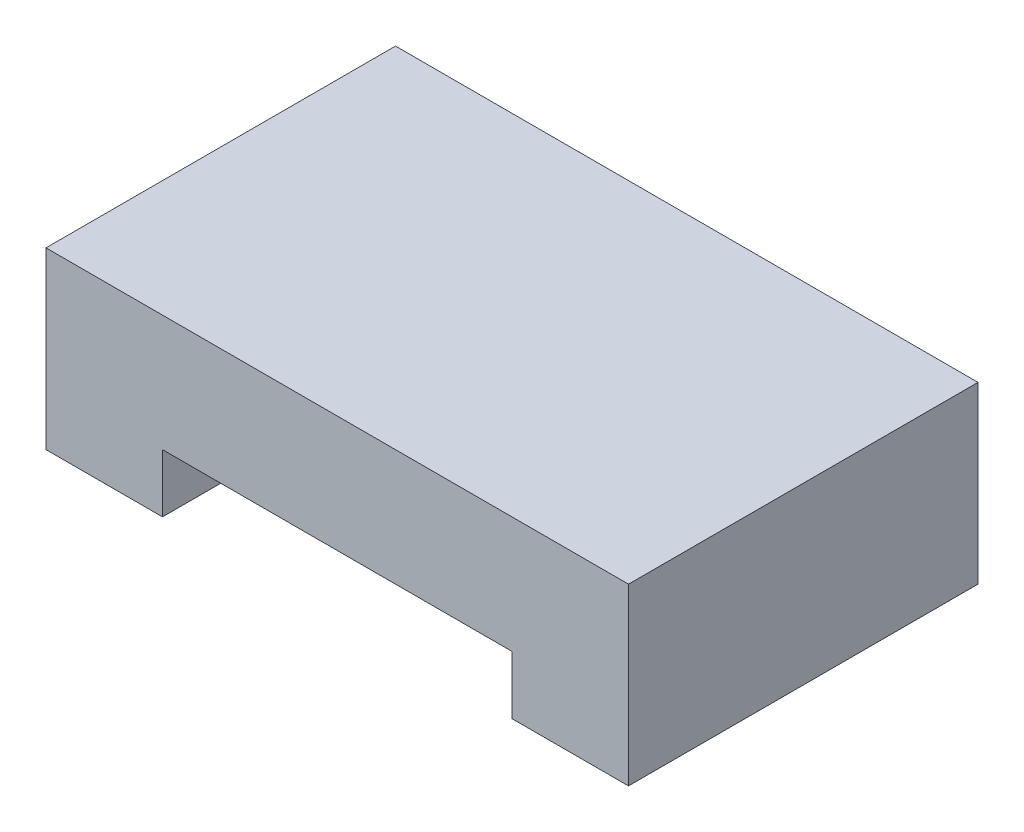
SolidWorks part; units mm, degrees
ref_plane "Front Plane" through (0, 0, 0) normal (0, 0, 1) x (1, 0, 0)
ref_plane "Top Plane" through (0, 0, 0) normal (0, 1, 0) x (1, 0, 0)
ref_plane "Right Plane" through (0, 0, 0) normal (1, 0, 0) x (0, 0, -1)
sketch "Sketch1" plane through (0, 0, 0) normal (0, 1, 0) x (1, 0, 0)
  line L1 (-2.5, -1.5) -> (2.5, -1.5)
  line L2 (-2.5, -1.5) -> (-2.5, 1.5)
  line L3 (-2.5, 1.5) -> (2.5, 1.5)
  line L4 (2.5, -1.5) -> (2.5, 1.5)
  line L5 (-2.5, -1.5) -> (2.5, 1.5) construction
  line L6 (-2.5, 1.5) -> (2.5, -1.5) construction
  point P0 (0, 0)
  dimension "D1" = 3
  dimension "D2" = 5
extrude "Boss-Extrude1" add sketch "Sketch1" along normal blind 1
sketch "Sketch2" plane through (0, 0, 0) normal (0, -1, 0) x (1, 0, 0)
  line L0 (2.5, -1.5) -> (-2.5, -1.5) construction
  line L1 (-2.5, 1.5) -> (-1.5, 1.5)
  line L2 (-2.5, 1.5) -> (-2.5, -1.5)
  line L3 (-2.5, -1.5) -> (-1.5, -1.5)
  line L4 (-1.5, 1.5) -> (-1.5, -1.5)
  line L6 (2.5, 1.5) -> (1.5, 1.5)
  line L7 (2.5, 1.5) -> (2.5, -1.5)
  line L8 (2.5, -1.5) -> (1.5, -1.5)
  line L9 (1.5, 1.5) -> (1.5, -1.5)
  dimension "D1" = 1
  dimension "D2" = 1
extrude "Boss-Extrude2" add sketch "Sketch2" along normal blind 1
chamfer "Chamfer1" distance 0.5 angle 45 8 edges at (2, -1, -1.5) (1.5, -1, 0) (2, -1, 1.5) (2.5, -1, 0) (-2, -1, 1.5) (-1.5, -1, 0) (-2, -1, -1.5) (-2.5, -1, 0)
